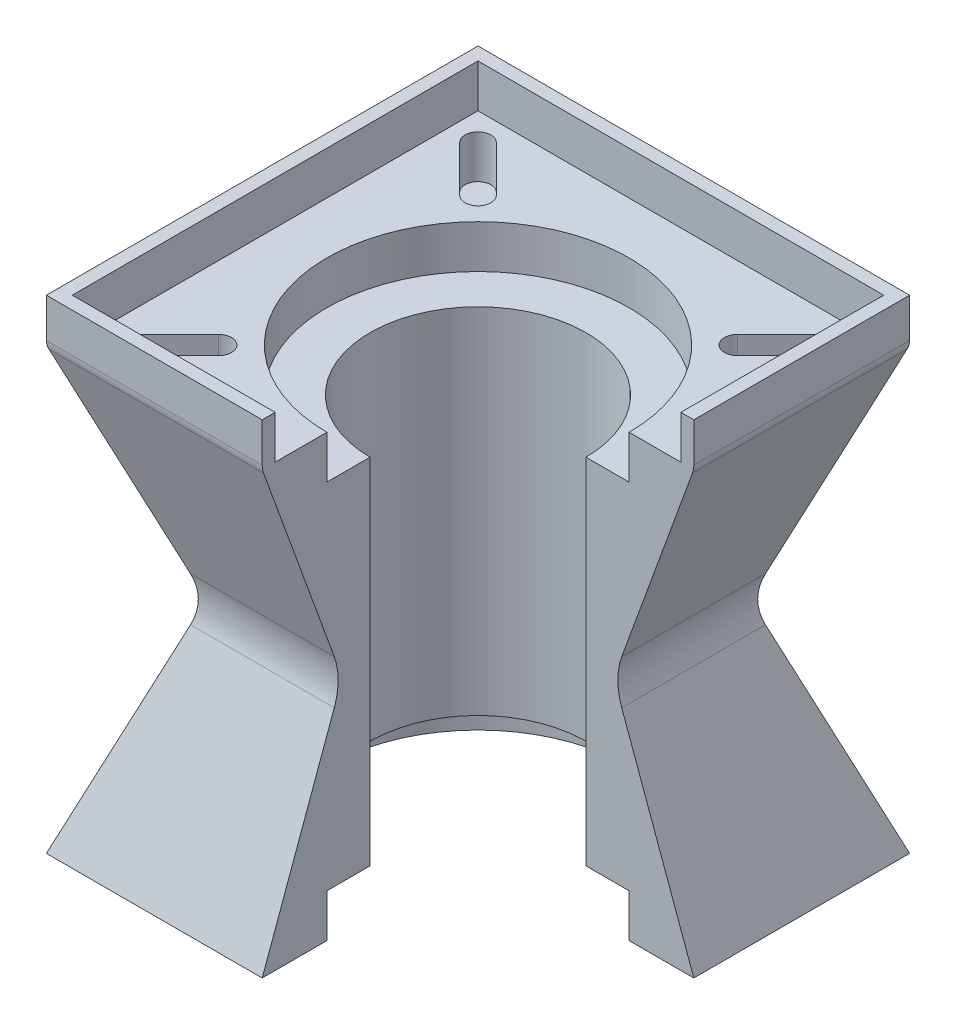
SolidWorks part; units mm, degrees
material "Cast Stainless Steel"
ref_plane "Front Plane" through (0, 0, 0) normal (0, 0, 1) x (1, 0, 0)
ref_plane "Top Plane" through (0, 0, 0) normal (0, 1, 0) x (1, 0, 0)
ref_plane "Right Plane" through (0, 0, 0) normal (1, 0, 0) x (0, 0, -1)
sketch "Sketch1" plane through (0, 0, 0) normal (0, 1, 0) x (1, 0, 0)
  line L1 (50, -50) -> (-50, -50)
  line L2 (50, -50) -> (50, 50)
  line L3 (50, 50) -> (-50, 50)
  line L4 (-50, -50) -> (-50, 50)
  line L5 (50, -50) -> (-50, 50) construction
  line L6 (50, 50) -> (-50, -50) construction
  point P0 (0, 0)
  dimension "D1" = 100
ref_plane "Plane1" through (0, -51, 0) normal (0, 1, 0) x (1, 0, 0)
sketch "Sketch3" plane through (0, 0, 0) normal (0, 0, 1) x (1, 0, 0)
  line L0 (0, 0) -> (-50, 0)
  line L1 (50, 0) -> (-50, 0) construction
  line L2 (50, 0) -> (-50, 0) construction
  line L3 (-50, 0) -> (-31.4375, -51)
  line L4 (55, -51) -> (-55, -51) construction
  line L5 (-31.4375, -51) -> (0, -51)
  line L6 (0, -51) -> (0, 0)
  line L7 (-50, 0) -> (-50, -25.5) construction
  point P11 (-27.7608, -51)
  dimension "D1" = 20
  dimension "D2" = 50
sketch "Sketch4" plane through (0, -51, 0) normal (0, 1, 0) x (1, 0, 0)
  line L0 (-31.4375, 0) -> (0, 0) construction
  line L1 (-31.4375, 0) -> (0, 0) construction
  line L2 (50, 50) -> (-50, -50) construction
  line L3 (31.4375, 31.4375) -> (-31.4375, 31.4375)
  line L4 (31.4375, 31.4375) -> (31.4375, -31.4375)
  line L5 (31.4375, -31.4375) -> (-31.4375, -31.4375)
  line L6 (-31.4375, 31.4375) -> (-31.4375, -31.4375)
  line L7 (31.4375, 31.4375) -> (-31.4375, -31.4375) construction
  line L8 (31.4375, -31.4375) -> (-31.4375, 31.4375) construction
  line L9 (-31.4375, 0) -> (-50, 0) construction
  line L10 (-50, -50) -> (-50, 50) construction
loft "Loft1" add profiles "Sketch4", "Sketch1" connector at (-31.4375, -51, -31.4375) connector at (-50, 0, -50)
sketch "Sketch5" plane through (0, 0, 0) normal (0, 1, 0) x (1, 0, 0)
  circle A0 centre (0, 0) radius 25
  dimension "D1" = 50
extrude "Cut-Extrude1" cut sketch "Sketch5" against normal through all both and the other way through all
sketch "Sketch6" plane through (0, 0, 0) normal (0, 1, 0) x (1, 0, 0)
  circle A0 centre (0, 0) radius 35
  dimension "D1" = 70
extrude "Cut-Extrude2" cut sketch "Sketch6" against normal blind 10
sketch "Sketch7" plane through (0, 0, 0) normal (0, 1, 0) x (1, 0, 0)
  line L1 (0, 0) -> (50, 0)
  line L2 (0, 0) -> (0, -50)
  line L3 (0, -50) -> (50, -50)
  line L4 (50, 0) -> (50, -50)
extrude "Cut-Extrude3" cut sketch "Sketch7" against normal through all both and the other way through all
mirror "Mirror2" about plane through (0, -51, 0) normal (0, 1, 0) of bodies 105
fillet "Fillet1" radius 15 4 edges
sketch "Sketch8" plane through (0, 0, 0) normal (0, 1, 0) x (1, 0, 0)
  line L0 (0, 0) -> (-50, 50) construction
  line L1 (-23.7267, 46.984) -> (-46.984, 23.7267) construction
  line L2 (-42.78, 38.5373) -> (-32.1734, 27.9307)
  line L3 (-38.5373, 42.78) -> (-27.9307, 32.1734)
  line L4 (38.5373, 42.78) -> (27.9307, 32.1734)
  line L5 (42.78, 38.5373) -> (32.1734, 27.9307)
  line L6 (42.78, -38.5373) -> (32.1734, -27.9307)
  line L7 (38.5373, -42.78) -> (27.9307, -32.1734)
  line L8 (-38.5373, -42.78) -> (-27.9307, -32.1734)
  line L9 (-42.78, -38.5373) -> (-32.1734, -27.9307)
  circle A0 centre (0, 0) radius 50 construction
  arc A1 (-38.5373, 42.78) -> (-42.78, 38.5373) centre (-40.6586, 40.6586) ccw
  arc A2 (-27.9307, 32.1734) -> (-32.1734, 27.9307) centre (-30.052, 30.052) cw
  arc A3 (32.1734, 27.9307) -> (27.9307, 32.1734) centre (30.052, 30.052) cw
  arc A4 (42.78, 38.5373) -> (38.5373, 42.78) centre (40.6586, 40.6586) ccw
  arc A5 (27.9307, -32.1734) -> (32.1734, -27.9307) centre (30.052, -30.052) cw
  arc A6 (38.5373, -42.78) -> (42.78, -38.5373) centre (40.6586, -40.6586) ccw
  arc A7 (-32.1734, -27.9307) -> (-27.9307, -32.1734) centre (-30.052, -30.052) cw
  arc A8 (-42.78, -38.5373) -> (-38.5373, -42.78) centre (-40.6586, -40.6586) ccw
  point P5 (-35.3553, 35.3553)
  point P13 (-35.3553, 35.3553)
  point P15 (-37.4767, 33.234)
  point P17 (-33.234, 37.4767)
  point P38 (0, 0)
  dimension "D1" = 100
  dimension "D2" = 6
  dimension "D3" = 7.5
  dimension "D4" = 4
extrude "Cut-Extrude4" cut sketch "Sketch8" against normal blind 10
sketch "Sketch9" plane through (0, 0, 0) normal (0, 1, 0) x (1, 0, 0)
  line L0 (47, 47) -> (-47, 47)
  line L1 (0, -50) -> (-50, -50)
  line L2 (50, 0) -> (50, 50)
  line L3 (50, 50) -> (-50, 50)
  line L4 (-50, -50) -> (-50, 50)
  line L6 (50, 50) -> (-50, -50) construction
  line L7 (-47, -47) -> (-47, 47)
  line L8 (0, -47) -> (-47, -47)
  line L9 (47, 0) -> (47, 47)
  line L10 (0, -50) -> (0, -47)
  line L11 (47, 0) -> (50, 0)
  line L12 (50, -50) -> (-50, -50) construction
  line L13 (47, -47) -> (-47, -47) construction
  line L14 (0, 0) -> (-50, 50) construction
  line L15 (47, -47) -> (47, 47) construction
  line L16 (50, -50) -> (50, 50) construction
  point P0 (0, 0)
  dimension "D1" = 3
extrude "Boss-Extrude1" add sketch "Sketch9" along normal blind 10
fillet "Fillet2" radius 5 4 edges
